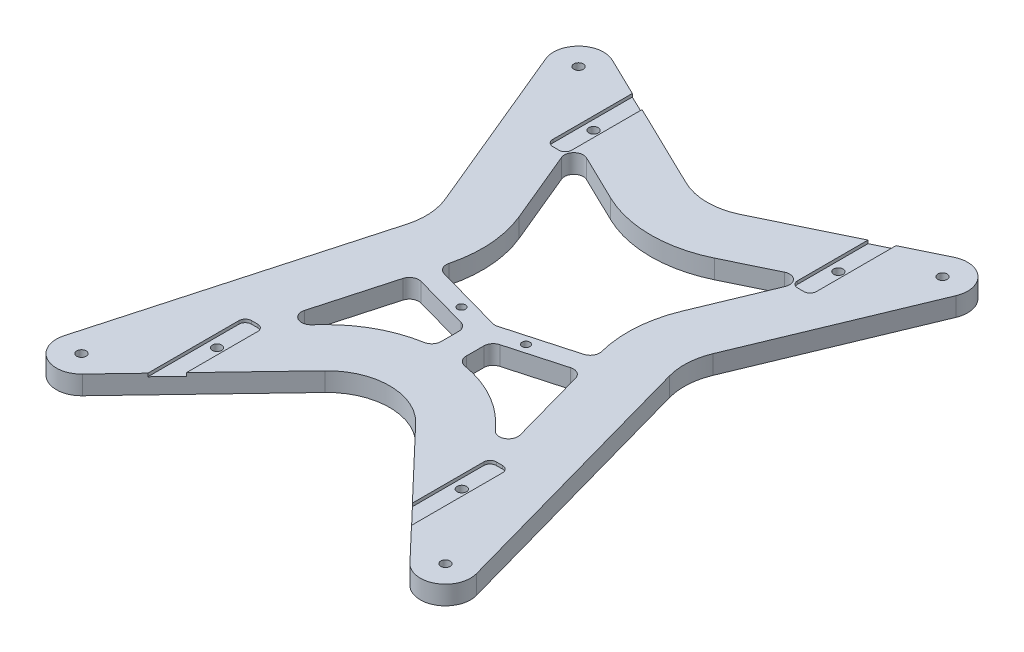
SolidWorks part; units mm, degrees
material "1060 Alloy"
ref_plane "Front Plane" through (0, 0, 0) normal (0, 0, 1) x (1, 0, 0)
ref_plane "Top Plane" through (0, 0, 0) normal (0, 1, 0) x (1, 0, 0)
ref_plane "Right Plane" through (0, 0, 0) normal (1, 0, 0) x (0, 0, -1)
sketch "Sketch1" plane through (0, 0, 0) normal (0, 1, 0) x (1, 0, 0)
  line L0 (-54.4954, 86.3958) -> (0, 60)
  line L1 (0, 60) -> (54.4954, 86.3958)
  line L2 (65.3716, 76.1292) -> (40, 15)
  line L3 (40, 15) -> (65.6883, -77.0455)
  line L4 (52.194, -84.7177) -> (0, -30)
  line L5 (0, -30) -> (-52.194, -84.7177)
  line L6 (-65.6883, -77.0455) -> (-40, 15)
  line L7 (-40, 15) -> (-65.3716, 76.1292)
  line L8 (-68.5894, 68.5894) -> (68.5894, -68.5894) construction
  line L9 (-42, 75) -> (-36, 75) construction
  line L10 (-42, 75) -> (-42, 55) construction
  line L11 (-42, 55) -> (-36, 55) construction
  line L12 (-36, 75) -> (-36, 55) construction
  line L13 (-42, 75) -> (-36, 55) construction
  line L14 (-42, 55) -> (-36, 75) construction
  line L15 (36, 75) -> (42, 75) construction
  line L16 (36, 75) -> (36, 55) construction
  line L17 (36, 55) -> (42, 55) construction
  line L18 (42, 75) -> (42, 55) construction
  line L19 (36, 75) -> (42, 55) construction
  line L20 (36, 55) -> (42, 75) construction
  line L21 (36, -45) -> (42, -45) construction
  line L22 (36, -45) -> (36, -65) construction
  line L23 (36, -65) -> (42, -65) construction
  line L24 (42, -45) -> (42, -65) construction
  line L25 (36, -45) -> (42, -65) construction
  line L26 (36, -65) -> (42, -45) construction
  line L27 (-42, -45) -> (-36, -45) construction
  line L28 (-42, -45) -> (-42, -65) construction
  line L29 (-42, -65) -> (-36, -65) construction
  line L30 (-36, -45) -> (-36, -65) construction
  line L31 (-42, -45) -> (-36, -65) construction
  line L32 (-42, -65) -> (-36, -45) construction
  line L33 (97, 40.1787) -> (40.1787, 97) construction
  line L34 (40.1787, 97) -> (-40.1787, 97) construction
  line L35 (-40.1787, 97) -> (-97, 40.1787) construction
  line L36 (-97, 40.1787) -> (-97, -40.1787) construction
  line L37 (-97, -40.1787) -> (-40.1787, -97) construction
  line L38 (-40.1787, -97) -> (40.1787, -97) construction
  line L39 (40.1787, -97) -> (97, -40.1787) construction
  line L40 (97, -40.1787) -> (97, 40.1787) construction
  line L41 (68.5894, 68.5894) -> (-68.5894, -68.5894) construction
  circle A0 centre (-57.9828, 79.196) radius 1.5
  circle A1 centre (57.9828, 79.196) radius 1.5
  circle A2 centre (-57.9828, -79.196) radius 1.5
  circle A3 centre (57.9828, -79.196) radius 1.5
  arc A4 (-54.4954, 86.3958) -> (-65.3716, 76.1292) centre (-57.9828, 79.196) ccw
  arc A5 (54.4954, 86.3958) -> (65.3716, 76.1292) centre (57.9828, 79.196) cw
  arc A6 (-65.6883, -77.0455) -> (-52.194, -84.7177) centre (-57.9828, -79.196) ccw
  arc A7 (65.6883, -77.0455) -> (52.194, -84.7177) centre (57.9828, -79.196) cw
  circle A8 centre (0, 0) radius 97 construction
  circle A9 centre (-39, 65) radius 1.5
  circle A10 centre (39, 65) radius 1.5
  circle A11 centre (39, -55) radius 1.5
  circle A12 centre (-39, -55) radius 1.5
  ellipse E0 centre (0, 15) end of major axis (0, 60) minor radius 40 construction
  dimension "D5" = 3
  dimension "D6" = 45
  dimension "D7" = 8
  dimension "D12" = 3
  dimension "D3" = 15
  dimension "D4" = 15
  dimension "D8" = 120
  dimension "D9" = 78
  dimension "D10" = 15
  dimension "D11" = 55
  dimension "D13" = 40
  dimension "D14" = 39
  dimension "D15" = 20
  dimension "D16" = 6
  dimension "D17" = 97
  dimension "D18" = 15
extrude "Boss-Extrude1" add sketch "Sketch1" along normal blind 6
fillet "Fillet1" radius 20 4 edges at (0, 3, -60) (-40, 3, -15) (0, 3, 30) (40, 3, -15)
sketch "Sketch2" plane through (0, 6, 0) normal (0, 1, 0) x (1, 0, 0)
  line L44 (-38.6591, 58.7249) -> (-26.025, 28.2848)
  line L45 (-24.5208, 3.5031) -> (-37.5911, -43.3302)
  line L46 (-37.5911, -43.3302) -> (-27.4967, -32.7477)
  line L47 (27.4967, -32.7477) -> (37.5911, -43.3302)
  line L48 (37.5911, -43.3302) -> (24.5208, 3.5031)
  line L49 (26.025, 28.2848) -> (38.6591, 58.7249)
  line L50 (38.6591, 58.7249) -> (16.5651, 48.0232)
  line L51 (-16.5651, 48.0232) -> (-38.6591, 58.7249)
  line L52 (-38.6591, 58.7249) -> (-26.025, 28.2848)
  line L53 (-24.5208, 3.5031) -> (-37.5911, -43.3302)
  line L54 (-37.5911, -43.3302) -> (-27.4967, -32.7477)
  line L55 (27.4967, -32.7477) -> (37.5911, -43.3302)
  line L56 (37.5911, -43.3302) -> (24.5208, 3.5031)
  line L57 (26.025, 28.2848) -> (38.6591, 58.7249)
  line L58 (38.6591, 58.7249) -> (16.5651, 48.0232)
  line L59 (-16.5651, 48.0232) -> (-38.6591, 58.7249)
  arc A40 (-24.5208, 3.5031) -> (-26.025, 28.2848) centre (-61.1221, 13.7179) ccw
  arc A41 (27.4967, -32.7477) -> (-27.4967, -32.7477) centre (0, -58.9762) ccw
  arc A42 (26.025, 28.2848) -> (24.5208, 3.5031) centre (61.1221, 13.7179) ccw
  arc A43 (-16.5651, 48.0232) -> (16.5651, 48.0232) centre (0, 82.2226) ccw
  arc A44 (-24.5208, 3.5031) -> (-26.025, 28.2848) centre (-61.1221, 13.7179) ccw
  arc A45 (27.4967, -32.7477) -> (-27.4967, -32.7477) centre (0, -58.9762) ccw
  arc A46 (26.025, 28.2848) -> (24.5208, 3.5031) centre (61.1221, 13.7179) ccw
  arc A47 (-16.5651, 48.0232) -> (16.5651, 48.0232) centre (0, 82.2226) ccw
  dimension "D1" = 18
extrude "Cut-Extrude1" cut sketch "Sketch2" against normal up to next
sketch "Sketch4" plane through (0, 6, 0) normal (0, 1, 0) x (1, 0, 0)
  line L0 (-8.7185, 64.223) -> (-54.4954, 86.3958) construction
  line L1 (-38, 53) -> (-40, 53)
  line L2 (-36, 55) -> (-36, 80.3435)
  line L3 (-36, 80.3435) -> (-42, 80.3435)
  line L4 (-42, 55) -> (-42, 80.3435)
  line L5 (54.4954, 86.3958) -> (8.7185, 64.223) construction
  line L6 (38, 53) -> (40, 53)
  line L7 (36, 55) -> (36, 80.3435)
  line L8 (36, 80.3435) -> (42, 80.3435)
  line L9 (42, 55) -> (42, 80.3435)
  line L10 (-52.194, -84.7177) -> (-14.4719, -45.1717) construction
  line L11 (-38, -43) -> (-40, -43)
  line L12 (-36, -45) -> (-36, -74.0308)
  line L13 (-36, -74.0308) -> (-42, -74.0308)
  line L14 (-42, -45) -> (-42, -74.0308)
  line L15 (14.4719, -45.1717) -> (52.194, -84.7177) construction
  line L16 (38, -43) -> (40, -43)
  line L17 (36, -45) -> (36, -74.0308)
  line L18 (36, -74.0308) -> (42, -74.0308)
  line L19 (42, -45) -> (42, -74.0308)
  circle A0 centre (-39, -55) radius 1.5 construction
  circle A1 centre (-39, 65) radius 1.5 construction
  circle A2 centre (39, -55) radius 1.5 construction
  arc A3 (40, -43) -> (42, -45) centre (40, -45) cw
  arc A4 (38, -43) -> (36, -45) centre (38, -45) ccw
  arc A5 (-40, -43) -> (-42, -45) centre (-40, -45) ccw
  arc A6 (-38, -43) -> (-36, -45) centre (-38, -45) cw
  arc A7 (40, 53) -> (42, 55) centre (40, 55) ccw
  arc A8 (38, 53) -> (36, 55) centre (38, 55) cw
  arc A9 (-38, 53) -> (-36, 55) centre (-38, 55) ccw
  arc A10 (-40, 53) -> (-42, 55) centre (-40, 55) cw
  dimension "D2" = 3
  dimension "D4" = 12
  dimension "D5" = 3
  dimension "D6" = 2
  dimension "D1" = 6
  dimension "D3" = 12
extrude "Cut-Extrude2" cut sketch "Sketch4" against normal blind 1
sketch "Sketch5" plane through (0, 6, 0) normal (0, 1, 0) x (1, 0, 0)
  line L0 (-25.1032, 1.416) -> (0, -5.5899)
  line L1 (-12.94, -8.43) -> (12.94, -8.43) construction
  line L2 (-12.94, -8.43) -> (-12.94, 8.43) construction
  line L3 (-12.94, 8.43) -> (12.94, 8.43) construction
  line L4 (12.94, -8.43) -> (12.94, 8.43) construction
  line L5 (-12.94, -8.43) -> (12.94, 8.43) construction
  line L6 (-12.94, 8.43) -> (12.94, -8.43) construction
  line L7 (-24.5208, 3.5031) -> (-37.5156, -43.0596) construction
  line L8 (0, -5.5899) -> (25.1032, 1.416)
  line L9 (37.5156, -43.0596) -> (24.5208, 3.5031) construction
  line L10 (25.1032, 1.416) -> (26.7161, -4.3632)
  line L11 (26.7161, -4.3632) -> (4, -10.7029)
  line L12 (4, -10.7029) -> (4, -21.1873)
  line L13 (-4, -21.1873) -> (-4, -10.7029)
  line L14 (-4, -10.7029) -> (-26.7161, -4.3632)
  line L15 (-26.7161, -4.3632) -> (-25.1032, 1.416)
  circle A0 centre (-10.3, -5.83) radius 1.25
  circle A1 centre (10.3, -5.83) radius 1.25
  arc A2 (27.4967, -32.7477) -> (-27.4967, -32.7477) centre (0, -58.9762) ccw construction
  arc A3 (4, -21.1873) -> (-4, -21.1873) centre (0, -58.9762) ccw
  point P0 (0, 0)
  dimension "D3" = 2.5
  dimension "D1" = 16.86
  dimension "D2" = 25.88
  dimension "D4" = 20.6
  dimension "D5" = 2.64
  dimension "D6" = 2.6
  dimension "D7" = 6
  dimension "D8" = 3
  dimension "D9" = 8
extrude "Boss-Extrude2" add sketch "Sketch5" against normal up to surface (6 mm away) up to face at (0, 0, -11.095)
fillet "Fillet2" radius 3 13 edges at (37.5911, 2.5, 43.3302) (-37.5911, 2.5, 43.3302) (38.6591, 2.5, -58.7249) (-38.6591, 2.5, -58.7249) (25.1032, 3, -1.416) (-25.1032, 3, -1.416) (0, 3, 5.5899) (26.7161, 3, 4.3632) (4, 3, 10.7029) (4, 3, 21.1873) (-4, 3, 21.1873) (-4, 3, 10.7029) (-26.7161, 3, 4.3632)
equation "\"D14@Sketch1\"=\"D9@Sketch1\"/2"
